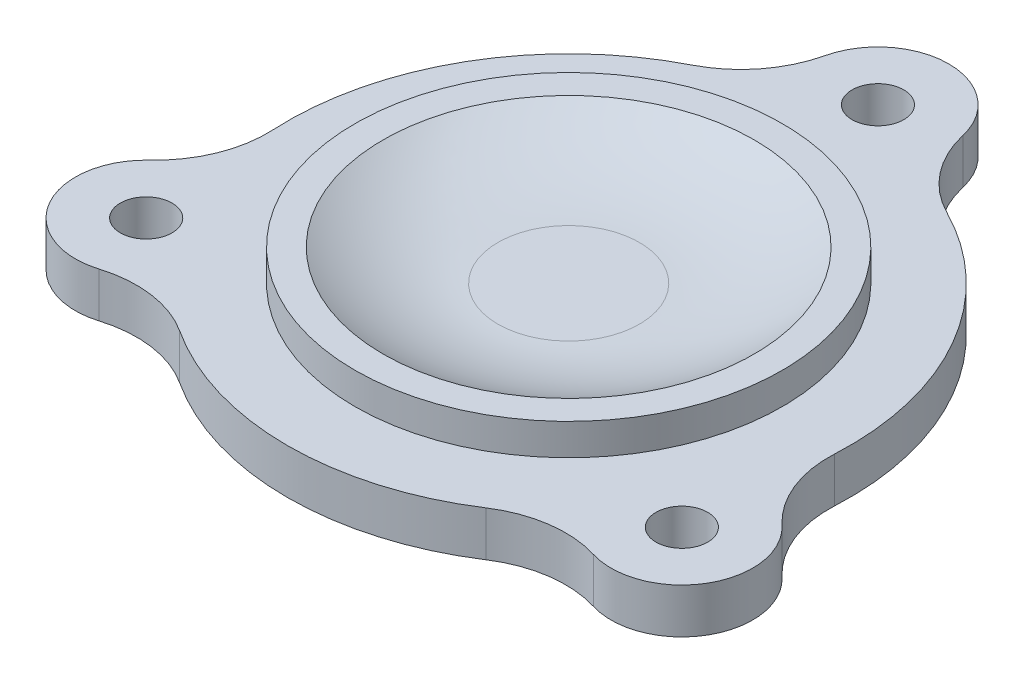
SolidWorks part; units mm, degrees
material "PETG"
ref_plane "Спереди" through (0, 0, 0) normal (0, 0, 1) x (1, 0, 0)
ref_plane "Сверху" through (0, 0, 0) normal (0, 1, 0) x (1, 0, 0)
ref_plane "Справа" through (0, 0, 0) normal (1, 0, 0) x (0, 0, -1)
sketch "Эскиз1" plane through (0, 0, 0) normal (0, 1, 0) x (1, 0, 0)
  circle A0 centre (0, 0) radius 9.5 construction
  circle A1 centre (0, 0) radius 12.5
  dimension "D1" = 19
  dimension "D2" = 3
extrude "Бобышка-Вытянуть1" add sketch "Эскиз1" along normal blind 2
sketch "Эскиз2" plane through (0, 2, 0) normal (0, 1, 0) x (1, 0, 0)
  circle A0 centre (0, 0) radius 9.5
  circle A1 centre (0, 0) radius 8.25
  dimension "D1" = 19
  dimension "D2" = 1.25
extrude "Бобышка-Вытянуть2" add sketch "Эскиз2" along normal blind 1.4
fillet "Скругление1" radius 10 1 edges at (0, 2, 8.25)
sketch "Эскиз3" plane through (0, 2, 0) normal (0, 1, 0) x (1, 0, 0)
  line L0 (0, 0) -> (0, 50000) construction
  line L1 (0, 0) -> (-50000, 0) construction
  circle A0 centre (0, 0) radius 12.5 construction
  arc A1 (5.6701, 11.14) -> (-5.6701, 11.14) centre (0, 0) ccw
  circle A2 centre (0, 13.75) radius 1.15
  arc A3 (3.0681, 14.4635) -> (-3.0681, 14.4635) centre (0, 13.75) ccw
  arc A4 (-3.0681, 14.4635) -> (-5.6701, 11.14) centre (-7.9382, 15.596) cw
  arc A5 (3.0681, 14.4635) -> (5.6701, 11.14) centre (7.9382, 15.596) ccw
  arc A6 (10.9917, -9.8888) -> (14.0598, -4.5747) centre (11.9078, -6.875) ccw
  arc A7 (14.0598, -4.5747) -> (12.4826, -0.6595) centre (17.4756, -0.9233) cw
  arc A8 (6.8125, -10.4805) -> (12.4826, -0.6595) centre (0, 0) ccw
  arc A9 (10.9917, -9.8888) -> (6.8125, -10.4805) centre (9.5374, -14.6727) ccw
  circle A10 centre (11.9078, -6.875) radius 1.15
  arc A11 (-14.0598, -4.5747) -> (-10.9917, -9.8888) centre (-11.9078, -6.875) ccw
  arc A12 (-10.9917, -9.8888) -> (-6.8125, -10.4805) centre (-9.5374, -14.6727) cw
  arc A13 (-12.4826, -0.6595) -> (-6.8125, -10.4805) centre (0, 0) ccw
  arc A14 (-14.0598, -4.5747) -> (-12.4826, -0.6595) centre (-17.4756, -0.9233) ccw
  circle A15 centre (-11.9078, -6.875) radius 1.15
  point P33 (0, 0)
  dimension "D1" = 2.3
  dimension "D2" = 2
  dimension "D3" = 1.25
  dimension "D4" = 5
  dimension "D5" = 3
extrude "Бобышка-Вытянуть3" add sketch "Эскиз3" against normal up to surface (2 mm away) up to face at (0, 0, 12.5)
